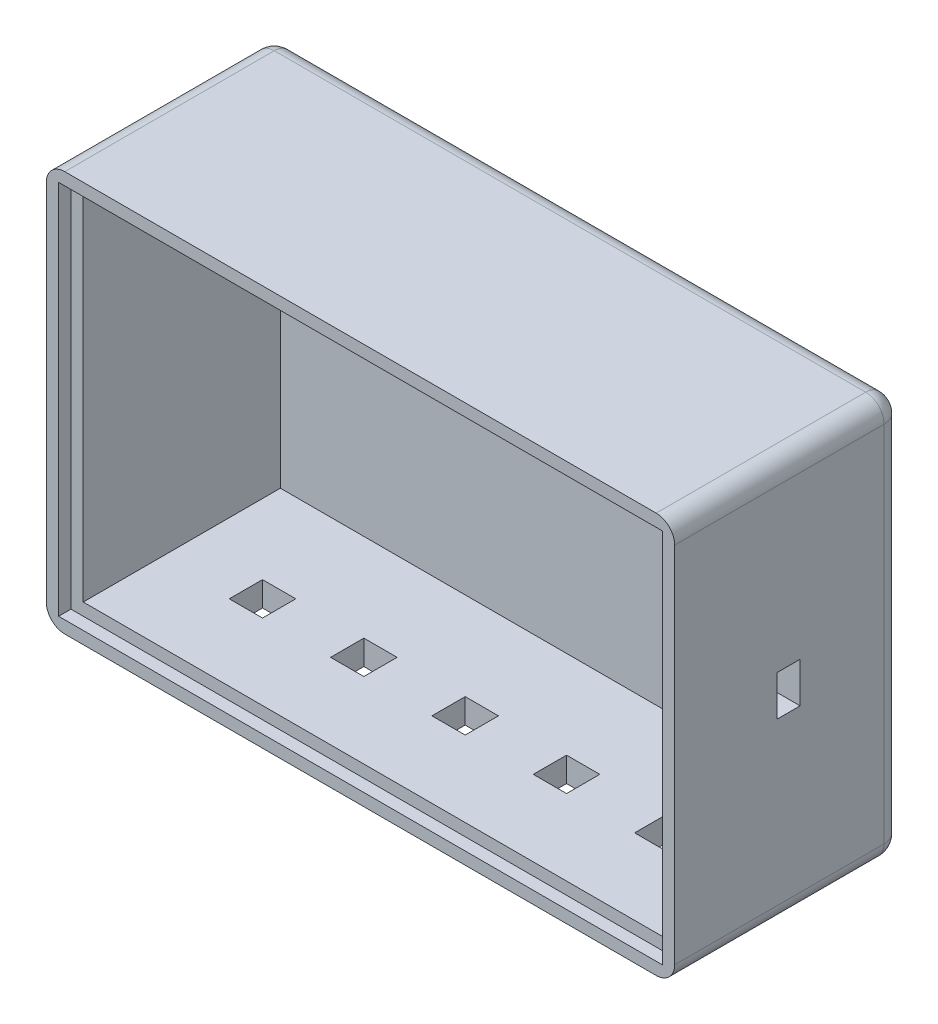
SolidWorks part; units mm, degrees
ref_plane "Přední rovina" through (0, 0, 0) normal (0, 0, 1) x (1, 0, 0)
ref_plane "Horní rovina" through (0, 0, 0) normal (0, 1, 0) x (1, 0, 0)
ref_plane "Pravá rovina" through (0, 0, 0) normal (1, 0, 0) x (0, 0, -1)
sketch "Skica1" plane through (0, 0, 0) normal (0, 0, 1) x (1, 0, 0)
  line L1 (0, 0) -> (98, 0)
  line L2 (0, 0) -> (0, 61)
  line L3 (0, 61) -> (98, 61)
  line L4 (98, 0) -> (98, 61)
  line L5 (-2, 63) -> (100, 63)
  line L6 (-2, 63) -> (-2, -2)
  line L7 (-2, -2) -> (100, -2)
  line L8 (100, 63) -> (100, -2)
  line L9 (2, 59) -> (96, 59)
  line L10 (2, 59) -> (2, 2)
  line L11 (2, 2) -> (96, 2)
  line L12 (96, 59) -> (96, 2)
  dimension "D1" = 102
  dimension "D2" = 65
  dimension "D3" = 2
  dimension "D4" = 2
  dimension "D5" = 2
  dimension "D6" = 2
  dimension "D7" = 2
  dimension "D8" = 2
  dimension "D9" = 2
  dimension "D10" = 2
  dimension "D11" = 57
  dimension "D12" = 94
extrude "Přidat vysunutím1" add sketch "Skica1" along normal blind 3 contours L6 L7 L8 L5
extrude "Přidat vysunutím2" add sketch "Skica1<4>" along normal blind 37 contours L8 L5 L6 L7 L4 L1 L2 L3 region at (49, 61.7905, 0)
sketch "Skica1<4>" plane through (0, 0, 0) normal (0, 0, 1) x (1, 0, 0) same geometry as "Skica1"
extrude "Přidat vysunutím3" add sketch "Skica1<5>" along normal blind 35 contours L1 L4 L3 L2 L9 L12 L11 L10 region at (1.1543, 30.5, 0)
sketch "Skica1<5>" plane through (0, 0, 0) normal (0, 0, 1) x (1, 0, 0) same geometry as "Skica1"
sketch "Skica2" plane through (100, 0, 0) normal (1, 0, 0) x (0, 0, -1)
  line L0 (-18.5, 63) -> (-18.5, -2) construction
  line L1 (-20.365, 27.225) -> (-16.635, 27.225)
  line L2 (-20.365, 27.225) -> (-20.365, 33.775)
  line L3 (-20.365, 33.775) -> (-16.635, 33.775)
  line L4 (-16.635, 27.225) -> (-16.635, 33.775)
  line L5 (-20.365, 27.225) -> (-16.635, 33.775) construction
  line L6 (-20.365, 33.775) -> (-16.635, 27.225) construction
  line L7 (-37, 63) -> (0, 63) construction
  line L8 (-37, -2) -> (0, -2) construction
  line L9 (-37, 30.5) -> (0, 30.5) construction
  line L10 (-37, 63) -> (-37, -2) construction
  line L11 (0, 63) -> (0, -2) construction
  point P0 (-18.5, 30.5)
  point P17 (-18.5, 30.5)
  dimension "D1" = 6.55
  dimension "D2" = 3.73
extrude "Odebrat vysunutím1" cut sketch "Skica2" against normal up to surface (4 mm away) up to face at (96, 30.5, 19)
fillet "Zaoblit1" radius 3 4 edges at (-2, 30.5, 0) (49, 63, 0) (100, 30.5, 0) (49, -2, 0)
sketch "Skica4" plane through (0, -2, 0) normal (0, -1, 0) x (1, 0, 0)
  line L0 (-2, 37) -> (-2, 3) construction
  line L1 (13.4, 22.7) -> (18.8, 22.7)
  line L2 (13.4, 22.7) -> (13.4, 17.3)
  line L3 (13.4, 17.3) -> (18.8, 17.3)
  line L4 (18.8, 22.7) -> (18.8, 17.3)
  line L5 (-2, 20) -> (100, 20) construction
  line L6 (100, 37) -> (100, 3) construction
  line L7 (-2, 37) -> (100, 37) construction
  line L8 (29.85, 22.7) -> (35.25, 22.7)
  line L9 (29.85, 22.7) -> (29.85, 17.3)
  line L10 (29.85, 17.3) -> (35.25, 17.3)
  line L11 (35.25, 22.7) -> (35.25, 17.3)
  line L12 (46.3, 22.7) -> (51.7, 22.7)
  line L13 (46.3, 22.7) -> (46.3, 17.3)
  line L14 (46.3, 17.3) -> (51.7, 17.3)
  line L15 (51.7, 22.7) -> (51.7, 17.3)
  line L16 (62.75, 22.7) -> (68.15, 22.7)
  line L17 (62.75, 22.7) -> (62.75, 17.3)
  line L18 (62.75, 17.3) -> (68.15, 17.3)
  line L19 (68.15, 22.7) -> (68.15, 17.3)
  line L20 (79.2, 22.7) -> (84.6, 22.7)
  line L21 (79.2, 22.7) -> (79.2, 17.3)
  line L22 (79.2, 17.3) -> (84.6, 17.3)
  line L23 (84.6, 22.7) -> (84.6, 17.3)
  line L24 (49, 37) -> (49, 3) construction
  line L25 (-2, 3) -> (100, 3) construction
  point P12 (13.4, 20)
  point P33 (0, 0)
  dimension "D1" = 5.4
  dimension "D2" = 5.4
  dimension "D4" = 5.4
  dimension "D5" = 5.4
  dimension "D6" = 5.4
  dimension "D7" = 5.4
  dimension "D8" = 11.05
  dimension "D9" = 11.05
  dimension "D10" = 11.05
  dimension "D11" = 11.05
fillet "Zaoblit2" radius 3 8 edges at (-1.1213, 62.1213, 0.8787) (99.1213, 62.1213, 0.8787) (99.1213, -1.1213, 0.8787) (-1.1213, -1.1213, 0.8787) (-2, 63, 20) (100, 63, 20) (100, -2, 20) (-2, -2, 20)
extrude "Odebrat vysunutím2" cut sketch "Skica4" against normal up to surface (4 mm away) up to face at (49, 2, 19)
